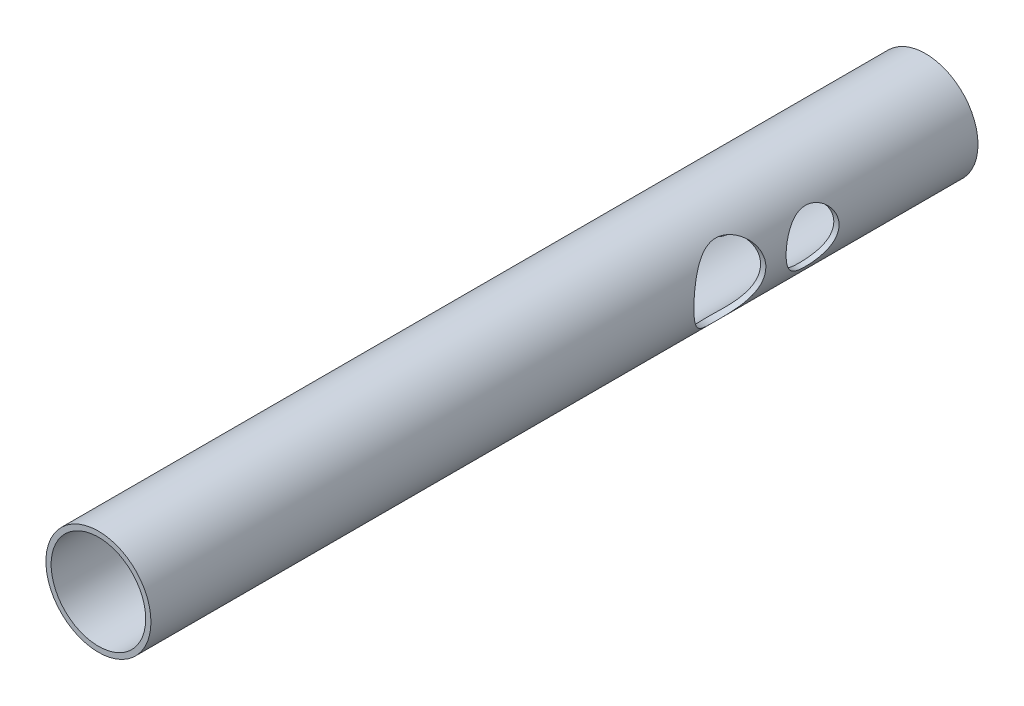
SolidWorks part; units mm, degrees
ref_plane "Front Plane" through (0, 0, 0) normal (0, 0, 1) x (1, 0, 0)
ref_plane "Top Plane" through (0, 0, 0) normal (0, 1, 0) x (1, 0, 0)
ref_plane "Right Plane" through (0, 0, 0) normal (1, 0, 0) x (0, 0, -1)
sketch "Sketch1" plane through (0, 0, 0) normal (0, 0, 1) x (1, 0, 0)
  circle A0 centre (0, 0) radius 31.75
  circle A1 centre (0, 0) radius 28.575
  dimension "D1" = 63.5
  dimension "D2" = 57.15
extrude "Boss-Extrude1" add sketch "Sketch1" along normal blind 250 and the other way blind 250 contours A1 | A0 region at (0, 0, 0)
sketch "Sketch2" plane through (0, 0, 0) normal (1, 0, 0) x (0, 0, -1)
  circle A0 centre (150, 0) radius 21.75
  circle A1 centre (100, 0) radius 16
  dimension "D1" = 32
  dimension "D2" = 43.5
  dimension "D3" = 150
  dimension "D4" = 100
extrude "Cut-Extrude1" cut sketch "Sketch2" against normal through all
sketch "Sketch3" plane through (0, 0, 0) normal (1, 0, 0) x (0, 0, -1)
  circle A0 centre (150, 0) radius 16
  circle A1 centre (100, 0) radius 21.75
  dimension "D1" = 43.5
  dimension "D2" = 32
  dimension "D3" = 100
  dimension "D4" = 150
extrude "Cut-Extrude2" cut sketch "Sketch3" along normal through all
